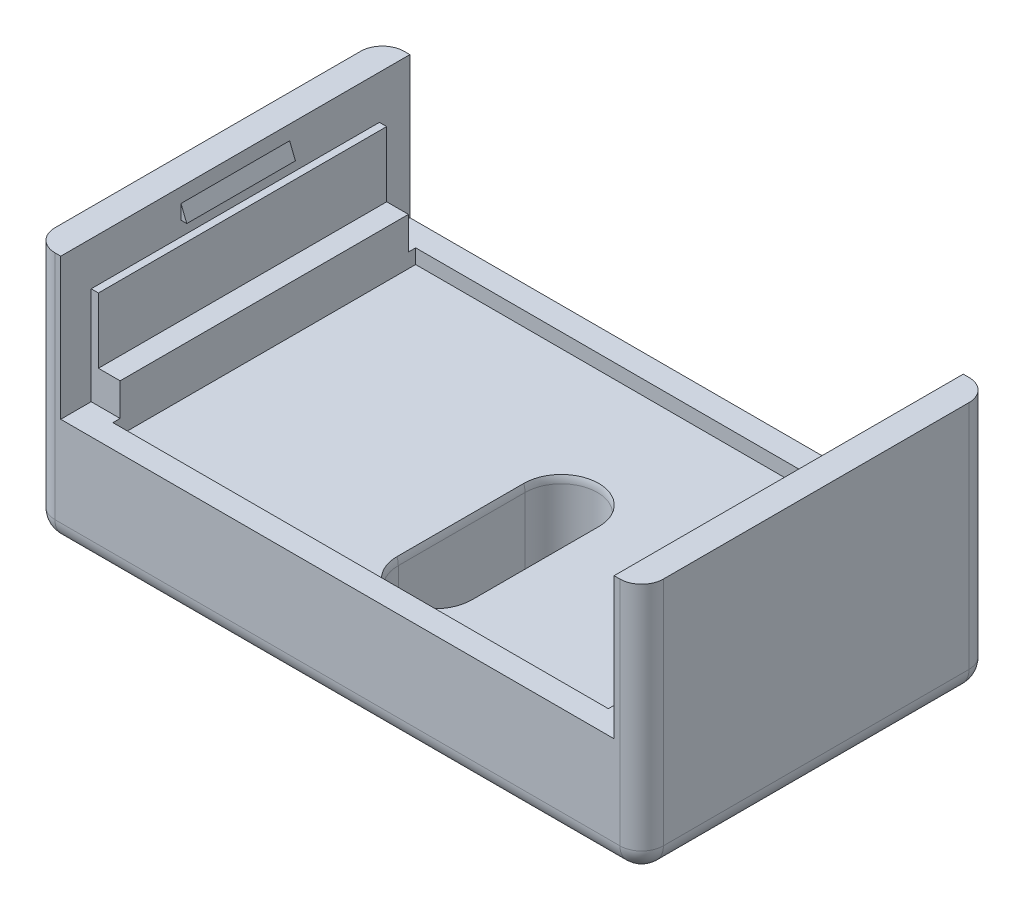
SolidWorks part; units mm, degrees
ref_plane "Alzado" through (0, 0, 0) normal (0, 0, 1) x (1, 0, 0)
ref_plane "Planta" through (0, 0, 0) normal (0, 1, 0) x (1, 0, 0)
ref_plane "Vista lateral" through (0, 0, 0) normal (1, 0, 0) x (0, 0, -1)
sketch "Sketch1" plane through (0, 0, 0) normal (0, 1, 0) x (1, 0, 0)
  line L1 (-34, -20.1) -> (34, -20.1)
  line L2 (-34, -20.1) -> (-34, 20.1)
  line L3 (-34, 20.1) -> (34, 20.1)
  line L4 (34, -20.1) -> (34, 20.1)
  line L5 (-34, -20.1) -> (34, 20.1) construction
  line L6 (-34, 20.1) -> (34, -20.1) construction
  point P0 (0, 0)
  dimension "D1" = 40.2
  dimension "D2" = 68
sketch "Sketch2" plane through (0, 0, 0) normal (0, 1, 0) x (1, 0, 0)
  line L20 (-42, 24.1) -> (42, 24.1)
  line L21 (42, -24.1) -> (-42, -24.1)
  line L22 (-34, -20.1) -> (34, -20.1) construction
  line L23 (-34, 20.1) -> (34, 20.1) construction
  line L24 (-42, 28.1) -> (-42, -28.1)
  line L25 (-42, -28.1) -> (42, -28.1)
  line L26 (42, -28.1) -> (42, 28.1)
  line L27 (42, 28.1) -> (-42, 28.1)
  line L28 (-42, 24.1) -> (-42, -24.1)
  line L30 (42, -24.1) -> (42, 24.1)
  dimension "D1" = 8
  dimension "D2" = 4
  dimension "D3" = 4
extrude "Boss-Extrude1" add sketch "Sketch2" along normal blind 3
sketch "Sketch3" plane through (0, 3, 0) normal (0, 1, 0) x (1, 0, 0)
  line L25 (-42, -24.1) -> (42, -24.1) construction
  line L26 (-42, 24.1) -> (-38.2, 24.1)
  line L27 (-42, 24.1) -> (-42, -24.1)
  line L28 (-42, -24.1) -> (-38.2, -24.1)
  line L32 (-38.2, 24.1) -> (-38.2, -24.1)
  line L33 (-42, 24.1) -> (-38.2, -24.1) construction
  line L34 (-42, -24.1) -> (-38.2, 24.1) construction
  line L36 (42, 24.1) -> (38.2, 24.1)
  line L37 (42, 24.1) -> (42, -24.1)
  line L38 (42, -24.1) -> (38.2, -24.1)
  line L39 (38.2, 24.1) -> (38.2, -24.1)
  line L40 (42, 24.1) -> (38.2, -24.1) construction
  line L41 (42, -24.1) -> (38.2, 24.1) construction
  point P8 (-40.1, 0)
  point P11 (40.1, 0)
  dimension "D2" = 3.8
  dimension "D1" = 3.8
extrude "Boss-Extrude2" add sketch "Sketch3" along normal blind 19
sketch "Sketch4" plane through (0, 3, 0) normal (0, 1, 0) x (1, 0, 0)
  line L17 (-38.2, 24.1) -> (-34.2, 24.1)
  line L18 (-38.2, 24.1) -> (-38.2, -24.1)
  line L19 (-38.2, -24.1) -> (-34.2, -24.1)
  line L20 (-34.2, 24.1) -> (-34.2, -24.1)
  line L21 (-38.2, 24.1) -> (-34.2, -24.1) construction
  line L22 (-38.2, -24.1) -> (-34.2, 24.1) construction
  line L23 (34, -20.1) -> (34, 20.1) construction
  line L24 (38.2, 24.1) -> (34.2, 24.1)
  line L25 (38.2, 24.1) -> (38.2, -24.1)
  line L26 (38.2, -24.1) -> (34.2, -24.1)
  line L27 (34.2, 24.1) -> (34.2, -24.1)
  line L28 (38.2, 24.1) -> (34.2, -24.1) construction
  line L29 (38.2, -24.1) -> (34.2, 24.1) construction
  line L30 (-34, -20.1) -> (-34, 20.1) construction
  line L31 (38.2, 24.1) -> (-38.2, 24.1) construction
  line L32 (-38.2, -24.1) -> (38.2, -24.1) construction
  line L33 (-38.2, -24.1) -> (-38.2, 24.1) construction
  line L34 (38.2, 24.1) -> (38.2, -24.1) construction
  point P5 (-36.2, 0)
  point P12 (36.2, 0)
  dimension "D1" = 0.2
  dimension "D2" = 0.2
extrude "Boss-Extrude3" add sketch "Sketch4" along normal blind 13
sketch "Sketch5" plane through (0, 0, 0) normal (0, 0, -1) x (-1, 0, 0)
  line L0 (-38.2, 20) -> (-37.4, 18)
  line L1 (-38.2, 22) -> (-38.2, 16) construction
  line L2 (-37.4, 18) -> (-38.2, 18)
  line L3 (-38.2, 20) -> (-38.2, 18)
  dimension "D1" = 0.8
  dimension "D2" = 2
  dimension "D3" = 2
extrude "Boss-Extrude4" add sketch "Sketch5" along normal mid plane 15
sketch "Sketch6" plane through (0, 16, 0) normal (0, 1, 0) x (1, 0, 0)
  line L1 (34.2, 24.1) -> (37.2, 24.1)
  line L2 (34.2, 24.1) -> (34.2, -24.1)
  line L3 (34.2, -24.1) -> (37.2, -24.1)
  line L4 (37.2, 24.1) -> (37.2, -24.1)
  line L5 (34.2, 24.1) -> (37.2, -24.1) construction
  line L6 (34.2, -24.1) -> (37.2, 24.1) construction
  line L8 (-34.2, 24.1) -> (-37.2, 24.1)
  line L9 (-34.2, 24.1) -> (-34.2, -24.1)
  line L10 (-34.2, -24.1) -> (-37.2, -24.1)
  line L11 (-37.2, 24.1) -> (-37.2, -24.1)
  line L12 (-34.2, 24.1) -> (-37.2, -24.1) construction
  line L13 (-34.2, -24.1) -> (-37.2, 24.1) construction
  line L14 (38.2, 24.1) -> (38.2, -24.1) construction
  line L15 (-38.2, -24.1) -> (-38.2, 24.1) construction
  point P4 (35.7, 0)
  point P12 (-35.7, 0)
  dimension "D1" = 1
  dimension "D2" = 1
extrude "Cut-Extrude1" cut sketch "Sketch6" against normal blind 9
mirror "Mirror1" about plane through (0, 0, 0) normal (1, 0, 0) of "Boss-Extrude4"
sketch "Sketch7" plane through (0, 3, 0) normal (0, 1, 0) x (1, 0, 0)
  line L0 (-34, -20.1) -> (-34, 20.1) construction
  line L1 (-34, -20.1) -> (34, -20.1) construction
  line L2 (34, -20.1) -> (34, 20.1) construction
  line L3 (-34, 20.1) -> (34, 20.1) construction
  line L4 (-34, -20.1) -> (-34, 20.1)
  line L5 (-34, -20.1) -> (34, -20.1)
  line L6 (34, -20.1) -> (34, 20.1)
  line L7 (-34, 20.1) -> (34, 20.1)
extrude "Cut-Extrude2" cut sketch "Sketch7" against normal blind 0.5
sketch "Sketch9" plane through (0, 2.5, 0) normal (0, 1, 0) x (1, 0, 0)
  line L1 (-42, 24.1) -> (42, 24.1)
  line L2 (-42, 24.1) -> (-42, -24.1)
  line L3 (-42, -24.1) -> (42, -24.1)
  line L4 (42, 24.1) -> (42, -24.1)
  line L5 (-42, 24.1) -> (42, -24.1) construction
  line L6 (-42, -24.1) -> (42, 24.1) construction
  point P4 (0, 0)
extrude "Boss-Extrude5" add sketch "Sketch9" against normal blind 15.4
sketch "Sketch10" plane through (0, 2.5, 0) normal (0, 1, 0) x (1, 0, 0)
  line L0 (29.6, 3.7) -> (29.6, 12.1) construction
  line L1 (25.1, 3.7) -> (25.1, 12.1)
  line L2 (34.1, 3.7) -> (34.1, 12.1)
  line L3 (34, -20.1) -> (34, 20.1) construction
  line L5 (34, 20.1) -> (-34, 20.1) construction
  arc A0 (25.1, 3.7) -> (34.1, 3.7) centre (29.6, 3.7) ccw
  arc A1 (34.1, 12.1) -> (25.1, 12.1) centre (29.6, 12.1) ccw
  point P2 (29.6, 7.9)
  dimension "D4" = 3.5
  dimension "D2" = 17.4
  dimension "D1" = 9
  dimension "D3" = 0.1
extrude "Cut-Extrude3" cut sketch "Sketch10" against normal blind 14 and the other way through all
sketch "Sketch11" plane through (0, 2.5, 0) normal (0, 1, 0) x (1, 0, 0)
  line L0 (4.6, 2.2) -> (4.6, -15.3) construction
  line L1 (9.6, 2.2) -> (9.6, -15.3)
  line L2 (-0.4, 2.2) -> (-0.4, -15.3)
  line L3 (34, -20.1) -> (34, 20.1) construction
  line L4 (-34, -20.1) -> (34, -20.1) construction
  arc A0 (9.6, 2.2) -> (-0.4, 2.2) centre (4.6, 2.2) ccw
  arc A1 (-0.4, -15.3) -> (9.6, -15.3) centre (4.6, -15.3) ccw
  point P2 (4.6, -6.55)
  dimension "D1" = 10
  dimension "D2" = 17.5
  dimension "D3" = 29.4
  dimension "D4" = 4.8
extrude "Cut-Extrude4" cut sketch "Sketch11" against normal through all both and the other way through all
fillet "Fillet1" radius 3 20 edges at (0, -12.9, 24.1) (42, -12.9, 0) (0, -12.9, -24.1) (-42, -12.9, 0) (-42, 4.55, 24.1) (42, 4.55, 24.1) (42, 4.55, -24.1) (-42, 4.55, -24.1) (29.1257, 2.5, 0.7749) (25.1, 2.5, -7.9) (4.6, 2.5, -7.2) (-0.4, 2.5, 6.55) (8.6, 2.5, 18.3) (0.6, 2.5, 18.3) (4.6, -12.9, -7.2) (9.6, -12.9, 6.55) (4.6, -12.9, 20.3) (29.1257, 2.5, -16.5749) (9.6, 2.5, 6.55) (-0.4, -12.9, 6.55)
sketch "Sketch12" plane through (0, 2.5, 0) normal (0, 1, 0) x (1, 0, 0)
  line L0 (38.2, -24.1) -> (38.2, 24.1) construction
  line L1 (-38.2, 24.1) -> (38.2, 24.1)
  line L2 (-38.2, 24.1) -> (-38.2, 19.9)
  line L3 (-38.2, 19.9) -> (38.2, 19.9)
  line L4 (38.2, 24.1) -> (38.2, 19.9)
  line L5 (-38.2, 24.1) -> (38.2, 19.9) construction
  line L6 (-38.2, 19.9) -> (38.2, 24.1) construction
  line L9 (-38.2, -24.1) -> (38.2, -24.1)
  line L10 (-38.2, -24.1) -> (-38.2, -19.9)
  line L11 (-38.2, -19.9) -> (38.2, -19.9)
  line L12 (38.2, -24.1) -> (38.2, -19.9)
  line L13 (-38.2, -24.1) -> (38.2, -19.9) construction
  line L14 (-38.2, -19.9) -> (38.2, -24.1) construction
  point P4 (0, 22)
  point P14 (0, -22)
  dimension "D1" = 4.2
  dimension "D2" = 4.2
extrude "Cut-Extrude5" cut sketch "Sketch12" along normal blind 20
sketch "Sketch13" plane through (0, 2.5, 0) normal (0, 1, 0) x (1, 0, 0)
  line L0 (34.2, 19.9) -> (34.2, -19.9) construction
  line L1 (-34.2, 20.9) -> (34.2, 20.9)
  line L2 (-34.2, 20.9) -> (-34.2, -20.9)
  line L3 (-34.2, -20.9) -> (34.2, -20.9)
  line L4 (34.2, 20.9) -> (34.2, -20.9)
  line L5 (-34.2, 20.9) -> (34.2, -20.9) construction
  line L6 (-34.2, -20.9) -> (34.2, 20.9) construction
  line L7 (-34.2, -19.9) -> (-34.2, 19.9) construction
  line L8 (-34.2, -19.9) -> (-37.2, -19.9) construction
  line L9 (-37.2, 19.9) -> (-34.2, 19.9) construction
  point P4 (0, 0)
  point P13 (-35.7, 19.9)
  dimension "D1" = 1
  dimension "D2" = 1
extrude "Cut-Extrude6" cut sketch "Sketch13" against normal blind 2 and the other way through all
